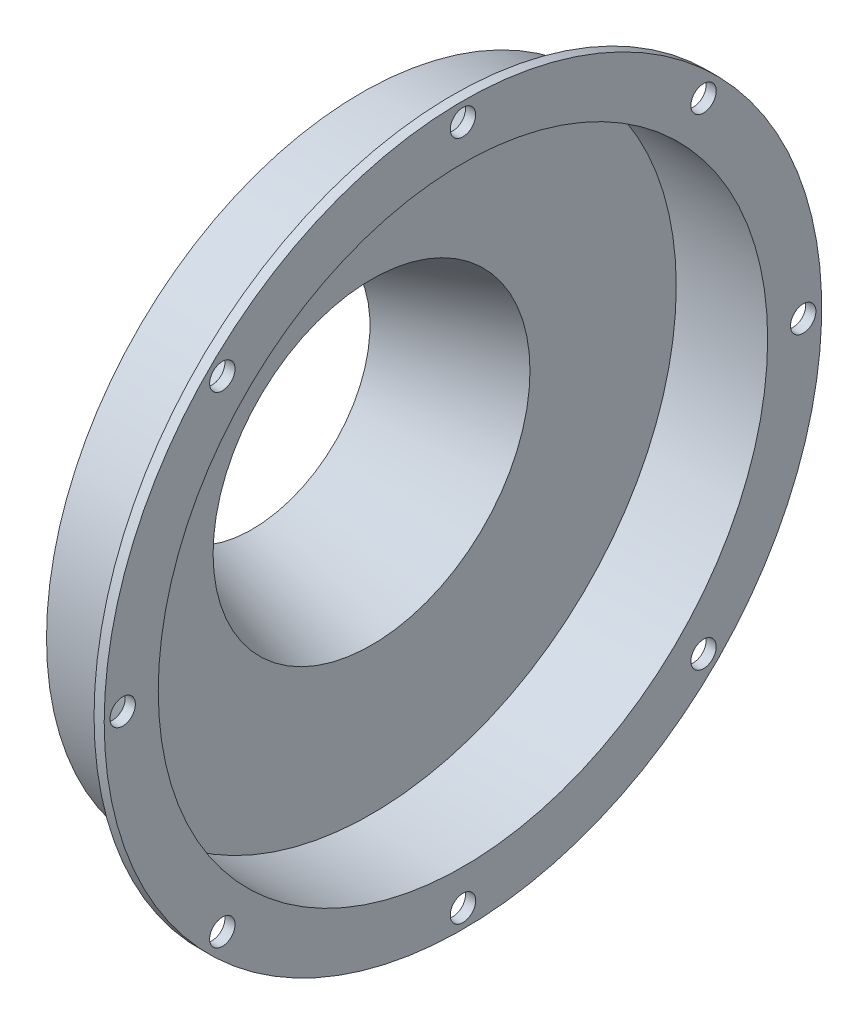
SolidWorks part; units mm, degrees
ref_plane "Front Plane" through (0, 0, 0) normal (0, 0, 1) x (1, 0, 0)
ref_plane "Top Plane" through (0, 0, 0) normal (0, 1, 0) x (1, 0, 0)
ref_plane "Right Plane" through (0, 0, 0) normal (1, 0, 0) x (0, 0, -1)
sketch "Sketch1" plane through (0, 0, 0) normal (0, 0, 1) x (1, 0, 0)
  line L0 (0, 0) -> (61.3012, 0) construction
  line L1 (0, 29.464) -> (29.845, 39.624)
  line L2 (29.845, 39.624) -> (29.845, 76.2)
  line L3 (29.845, 76.2) -> (52.705, 76.2)
  line L4 (52.705, 76.2) -> (52.705, 89.7128)
  line L5 (-0.8186, 31.8685) -> (27.305, 41.4425)
  line L6 (27.305, 41.4425) -> (27.305, 78.74)
  line L7 (27.305, 78.74) -> (50.165, 78.74)
  line L8 (50.165, 78.74) -> (50.165, 89.7128)
  line L9 (-0.8186, 31.8685) -> (0, 29.464)
  line L10 (50.165, 89.7128) -> (52.705, 89.7128)
  point P5 (30.6506, 0)
  dimension "D1" = 29.464
  dimension "D2" = 39.624
  dimension "D3" = 29.845
  dimension "D4" = 76.2
  dimension "D5" = 89.7128
  dimension "D7" = 22.86
  dimension "D6" = 2.54
revolve "Revolve1" add sketch "Sketch1" angle 360 about L0
sketch "Sketch2" plane through (50.165, 0, 0) normal (-1, 0, 0) x (0, 0, 1)
  circle A0 centre (0, 85.09) radius 3.175
  dimension "D1" = 6.35
  dimension "D2" = 85.09
extrude "Cut-Extrude1" cut sketch "Sketch2" against normal blind 2.54
pattern_circular "CirPattern1" count 8 over 360 about axis through (50.165, 0, 0) along (-1, 0, 0) of "Cut-Extrude1"
